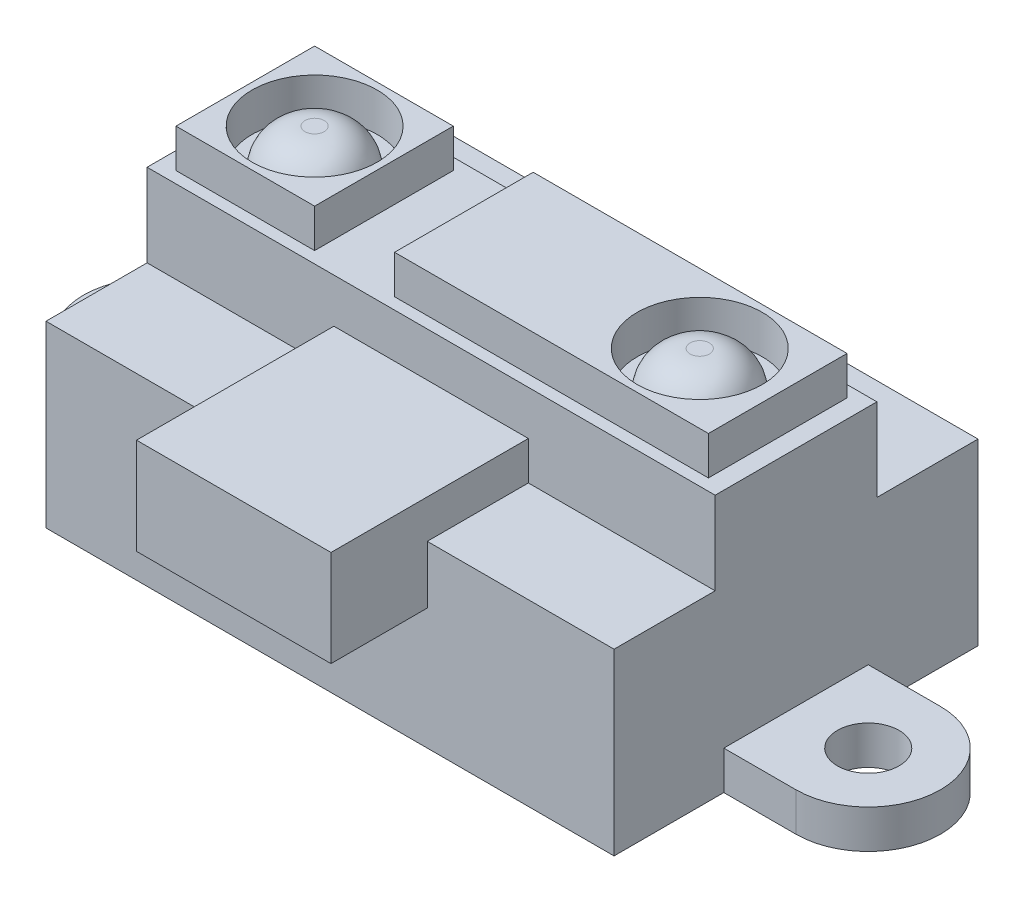
SolidWorks part; units mm, degrees
ref_plane "Face" through (0, 0, 0) normal (0, 0, 1) x (1, 0, 0)
ref_plane "Dessus" through (0, 0, 0) normal (0, 1, 0) x (1, 0, 0)
ref_plane "Droite" through (0, 0, 0) normal (1, 0, 0) x (0, 0, -1)
sketch "Esquisse1" plane through (0, 0, 0) normal (0, 1, 0) x (1, 0, 0)
  line L1 (0, 0) -> (29.5, 0)
  line L2 (0, 0) -> (0, 18.9)
  line L3 (0, 18.9) -> (29.5, 18.9)
  line L4 (29.5, 0) -> (29.5, 18.9)
  dimension "D1" = 29.5
  dimension "D2" = 18.9
extrude "Extrusion1" add sketch "Esquisse1" along normal blind 9.3
sketch "Esquisse2" plane through (0, 9.3, 0) normal (0, 1, 0) x (1, 0, 0)
  line L0 (0, 9.45) -> (29.5, 9.45) construction
  line L1 (0, 18.9) -> (0, 0) construction
  line L2 (29.5, 0) -> (29.5, 18.9) construction
  line L3 (0, 5.25) -> (29.5, 5.25)
  line L5 (0, 5.25) -> (0, 13.65)
  line L6 (0, 13.65) -> (29.5, 13.65)
  line L7 (29.5, 5.25) -> (29.5, 13.65)
  dimension "D1" = 8.4
extrude "Extrusion2" add sketch "Esquisse2" along normal blind 4.3
sketch "Esquisse3" plane through (0, 13.6, 0) normal (0, 1, 0) x (1, 0, 0)
  line L0 (0, 9.45) -> (29.5, 9.45) construction
  line L1 (0, 13.65) -> (0, 5.25) construction
  line L2 (29.5, 5.25) -> (29.5, 13.65) construction
  line L3 (4.5, 13.65) -> (4.5, 5.25) construction
  line L4 (29.5, 13.65) -> (0, 13.65) construction
  line L5 (0, 5.25) -> (29.5, 5.25) construction
  line L6 (24.5, 13.65) -> (24.5, 5.25) construction
  line L7 (29.5, 13.65) -> (0, 13.65) construction
  line L8 (0, 5.25) -> (29.5, 5.25) construction
  line L9 (0.9, 5.85) -> (8.1, 5.85)
  line L10 (0.9, 13.05) -> (8.1, 13.05)
  line L11 (0.9, 13.05) -> (0.9, 5.85)
  line L12 (8.1, 13.05) -> (8.1, 5.85)
  line L13 (12.25, 13.05) -> (12.25, 5.85)
  line L14 (12.25, 13.05) -> (28.55, 13.05)
  line L15 (12.25, 5.85) -> (28.55, 5.85)
  line L16 (28.55, 13.05) -> (28.55, 5.85)
  circle A0 centre (4.5, 9.45) radius 3.25
  circle A2 centre (24.5, 9.45) radius 3.25
  dimension "D4" = 6.5
  dimension "D1" = 4.5
  dimension "D2" = 20
  dimension "D3" = 7.2
  dimension "D6" = 4.15
  dimension "D7" = 16.3
extrude "Extrusion3" add sketch "Esquisse3" along normal blind 2
sketch "Esquisse4" plane through (0, 13.6, 0) normal (0, 1, 0) x (1, 0, 0)
  circle A0 centre (4.5, 9.45) radius 2.5
  circle A1 centre (4.5, 9.45) radius 3.25 construction
  circle A2 centre (24.5, 9.45) radius 2.5
  dimension "D1" = 5
extrude "Extrusion4" add sketch "Esquisse4" along normal blind 2
fillet "Congé1" radius 2 2 edges at (4.5, 15.6, -6.95) (24.5, 15.6, -6.95)
sketch "Esquisse5" plane through (0, 0, 0) normal (0, -1, 0) x (1, 0, 0)
  line L0 (29.5, -9.45) -> (0, -9.45) construction
  line L1 (29.5, 0) -> (29.5, -18.9) construction
  line L2 (0, -18.9) -> (0, 0) construction
  line L3 (14.75, 0) -> (14.75, -18.9) construction
  line L4 (0, 0) -> (29.5, 0) construction
  line L5 (29.5, -18.9) -> (0, -18.9) construction
  line L6 (0, -5.7) -> (-3.75, -5.7)
  line L7 (0, -9.45) -> (-7.5, -9.45) construction
  line L8 (-3.75, -9.45) -> (-3.75, -5.7) construction
  line L9 (0, -5.7) -> (0, -13.2)
  line L10 (0, -13.2) -> (-3.75, -13.2)
  line L11 (29.5, -5.7) -> (33.25, -5.7)
  line L12 (29.5, -5.7) -> (29.5, -13.2)
  line L13 (29.5, -13.2) -> (33.25, -13.2)
  arc A0 (-3.75, -5.7) -> (-3.75, -13.2) centre (-3.75, -9.45) ccw
  circle A1 centre (-3.75, -9.45) radius 1.6
  circle A2 centre (33.25, -9.45) radius 1.6
  arc A3 (33.25, -5.7) -> (33.25, -13.2) centre (33.25, -9.45) cw
  dimension "D1" = 3.2
  dimension "D2" = 3.75
  dimension "D3" = 3.75
extrude "Extrusion5" add sketch "Esquisse5" against normal blind 2
sketch "Esquisse6" plane through (0, 9.3, 0) normal (0, 1, 0) x (1, 0, 0)
  line L0 (14.75, 0) -> (14.75, 18.9) construction
  line L1 (0, 0) -> (29.5, 0) construction
  line L2 (29.5, 18.9) -> (0, 18.9) construction
  line L3 (19.8, 5.25) -> (9.7, 5.25)
  line L4 (0, 5.25) -> (29.5, 5.25) construction
  line L5 (9.7, 5.25) -> (9.7, -5)
  line L6 (0, 5.25) -> (29.5, 5.25) construction
  line L7 (9.7, -5) -> (19.8, -5)
  line L8 (19.8, 5.25) -> (19.8, -5)
  point P15 (14.75, 5.25)
  point P16 (14.75, -5)
  dimension "D1" = 10.1
  dimension "D2" = 5
extrude "Extrusion6" add sketch "Esquisse6" along normal blind 2
sketch "Esquisse7" plane through (0, 9.3, 0) normal (0, -1, 0) x (1, 0, 0)
  line L1 (19.8, 5) -> (9.7, 5)
  line L2 (19.8, 5) -> (19.8, 0)
  line L3 (19.8, 0) -> (9.7, 0)
  line L4 (9.7, 5) -> (9.7, 0)
extrude "Extrusion7" add sketch "Esquisse7" along normal blind 3
